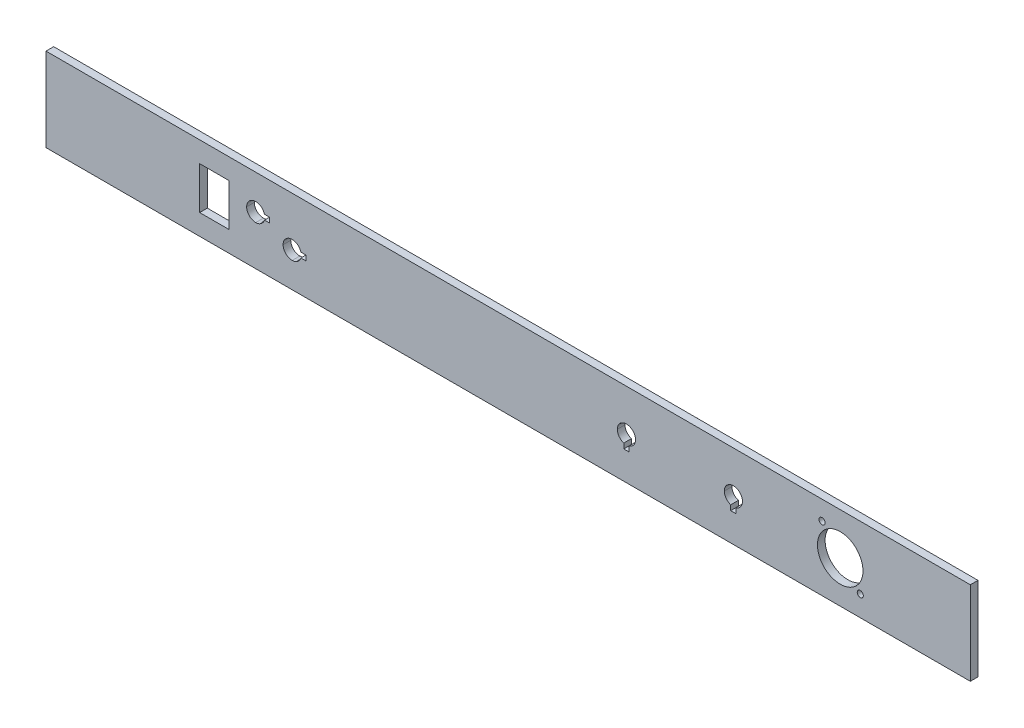
SolidWorks part; units mm, degrees
ref_plane "Front Plane" through (0, 0, 0) normal (0, 0, 1) x (1, 0, 0)
ref_plane "Top Plane" through (0, 0, 0) normal (0, 1, 0) x (1, 0, 0)
ref_plane "Right Plane" through (0, 0, 0) normal (1, 0, 0) x (0, 0, -1)
sketch "Sketch1" plane through (0, 0, 0) normal (0, 0, 1) x (1, 0, 0)
  line L1 (241.5, -21.85) -> (-241.5, -21.85)
  line L2 (241.5, -21.85) -> (241.5, 21.85)
  line L3 (241.5, 21.85) -> (-241.5, 21.85)
  line L4 (-241.5, -21.85) -> (-241.5, 21.85)
  line L5 (241.5, -21.85) -> (-241.5, 21.85) construction
  line L6 (241.5, 21.85) -> (-241.5, -21.85) construction
  point P0 (0, 0)
  dimension "D1" = 483
  dimension "D2" = 43.7
extrude "Boss-Extrude1" add sketch "Sketch1" along normal blind 4
sketch "Sketch2" plane through (0, 0, 4) normal (0, 0, 1) x (1, 0, 0)
  line L0 (-161.2079, -11.0681) -> (-161.2079, 11.0681)
  line L1 (-161.2079, 11.0681) -> (-145.7905, 11.0681)
  line L2 (-145.7905, 11.0681) -> (-145.7905, -11.0681)
  line L3 (-145.7905, -11.0681) -> (-161.2079, -11.0681)
  line L4 (-127.3683, 2.4325) -> (-124.689, 2.4325)
  line L5 (-124.689, 2.4325) -> (-124.689, 5.0746)
  line L6 (-124.689, 5.0746) -> (-127.3404, 5.0746)
  line L7 (-108.3216, -5.1862) -> (-105.6423, -5.1862)
  line L8 (-105.6423, -5.1862) -> (-105.6423, -2.5441)
  line L9 (-105.6423, -2.5441) -> (-108.2937, -2.5441)
  line L10 (-105.6423, -5.1862) -> (-105.6423, -11.0681) construction
  line L11 (-105.6423, -11.0681) -> (-161.2079, -11.0681) construction
  line L12 (-241.5, 0) -> (241.5, 0) construction
  line L13 (-241.5, 21.85) -> (-241.5, -21.85) construction
  line L14 (241.5, -21.85) -> (241.5, 21.85) construction
  line L15 (-161.2079, 0) -> (-144.5528, 0) construction
  line L16 (173.5, 11.9) -> (173.5, -11.9) construction
  line L17 (-203.5, 21.85) -> (-203.5, -21.85) construction
  line L18 (241.5, 21.85) -> (-241.5, 21.85) construction
  line L19 (-241.5, -21.85) -> (241.5, -21.85) construction
  line L20 (0, 0) -> (0, 21.85) construction
  line L21 (-131.9175, 8.5539) -> (-131.9175, -0.9445) construction
  line L22 (0, 0) -> (0, 21.85) construction
  line L23 (173.5, 11.9) -> (183.0068, 11.9) construction
  line L24 (163.0068, -13.5) -> (173.5, -13.5) construction
  line L25 (203.5, 21.85) -> (203.5, -21.85) construction
  line L26 (173.5, -13.5) -> (173.5, -11.9) construction
  line L27 (116.299, -7.2285) -> (118.941, -7.2285)
  line L28 (118.941, -7.2285) -> (118.941, -4.5771)
  line L29 (116.299, -4.5492) -> (116.299, -7.2285)
  line L30 (117.62, -7.2285) -> (117.62, 4.9318) construction
  line L31 (60.419, -7.2285) -> (63.061, -7.2285)
  line L32 (60.419, -4.5492) -> (60.419, -7.2285)
  line L33 (63.061, -7.2285) -> (63.061, -4.5771)
  line L34 (61.74, -7.2285) -> (61.74, 4.9318) construction
  line L35 (-153.4992, 11.0681) -> (-153.4992, 0) construction
  circle A0 centre (173.5, 0) radius 11.9
  circle A3 centre (183.9932, -11.1) radius 1.6
  circle A4 centre (163.9932, 11.9) radius 1.6
  spline S0 degree 3 poles (-136.6621, 3.8093) (-136.6621, 1.1878) (-134.5391, -0.9445) (-131.9175, -0.9445) knots 0 0 0 0 1 1 1 1
  spline S1 degree 3 poles (-131.9175, -0.9445) (-129.7741, -0.9445) (-127.9579, 0.4814) (-127.3683, 2.4325) knots 0 0 0 0 1 1 1 1
  spline S2 degree 3 poles (-127.3404, 5.0746) (-127.8969, 7.0777) (-129.7371, 8.5539) (-131.9175, 8.5539) knots 0 0 0 0 1 1 1 1
  spline S3 degree 3 poles (-131.9175, 8.5539) (-134.5391, 8.5539) (-136.6621, 6.4309) (-136.6621, 3.8093) knots 0 0 0 0 1 1 1 1
  spline S4 degree 3 poles (-117.6154, -3.8093) (-117.6154, -6.4309) (-115.4924, -8.5632) (-112.8708, -8.5632) knots 0 0 0 0 1 1 1 1
  spline S5 degree 3 poles (-112.8708, -8.5632) (-110.7274, -8.5632) (-108.9111, -7.1373) (-108.3216, -5.1862) knots 0 0 0 0 1 1 1 1
  spline S6 degree 3 poles (-108.2937, -2.5441) (-108.8502, -0.541) (-110.6903, 0.9352) (-112.8708, 0.9352) knots 0 0 0 0 1 1 1 1
  spline S7 degree 3 poles (-112.8708, 0.9352) (-115.4924, 0.9352) (-117.6154, -1.1878) (-117.6154, -3.8093) knots 0 0 0 0 1 1 1 1
  spline S8 degree 3 poles (122.4204, 0) (122.4204, 2.6216) (120.2974, 4.7446) (117.6758, 4.7446) knots 0 0 0 0 1 1 1 1
  spline S9 degree 3 poles (112.9219, 0) (112.9219, -2.1434) (114.3479, -3.9597) (116.299, -4.5492) knots 0 0 0 0 1 1 1 1
  spline S10 degree 3 poles (118.941, -4.5771) (120.9442, -4.0206) (122.4204, -2.1805) (122.4204, 0) knots 0 0 0 0 1 1 1 1
  spline S11 degree 3 poles (117.6758, 4.7446) (115.0542, 4.7446) (112.9219, 2.6216) (112.9219, 0) knots 0 0 0 0 1 1 1 1
  spline S12 degree 3 poles (61.7958, 4.7446) (59.1742, 4.7446) (57.0419, 2.6216) (57.0419, 0) knots 0 0 0 0 1 1 1 1
  spline S13 degree 3 poles (66.5404, 0) (66.5404, 2.6216) (64.4174, 4.7446) (61.7958, 4.7446) knots 0 0 0 0 1 1 1 1
  spline S14 degree 3 poles (57.0419, 0) (57.0419, -2.1434) (58.4679, -3.9597) (60.419, -4.5492) knots 0 0 0 0 1 1 1 1
  spline S15 degree 3 poles (63.061, -4.5771) (65.0642, -4.0206) (66.5404, -2.1805) (66.5404, 0) knots 0 0 0 0 1 1 1 1
  dimension "D10" = 23
  dimension "D1" = 38
  dimension "D2" = 55.88
  dimension "D3" = 19.0467
  dimension "D4" = 48.3371
  dimension "D5" = 9.3217
  dimension "D6" = 2.6421
  dimension "D7" = 2.6793
  dimension "D8" = 9.4985
  dimension "D9" = 30
extrude "Cut-Extrude1" cut sketch "Sketch2" against normal blind 4
